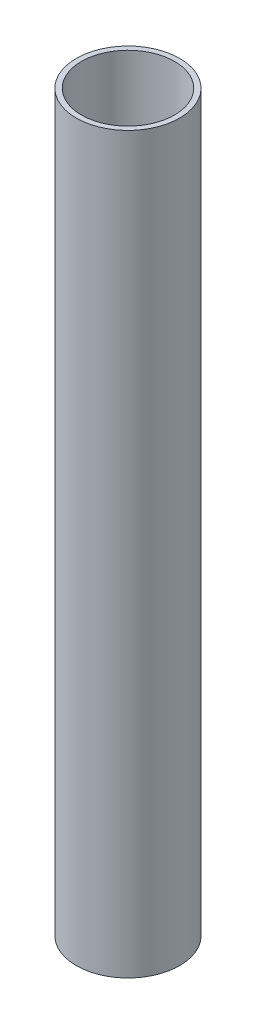
SolidWorks part; units mm, degrees
other "Boss-Extrude"
material "Toray T700"
ref_plane "Front" through (0, 0, 0) normal (0, 0, 1) x (1, 0, 0)
ref_plane "Top" through (0, 0, 0) normal (0, 1, 0) x (1, 0, 0)
ref_plane "Right" through (0, 0, 0) normal (1, 0, 0) x (0, 0, -1)
sketch "Sketch1" plane through (0, 0, 0) normal (0, 1, 0) x (1, 0, 0)
  line L5 (4.7969, 0) -> (-5.97, 0) construction
  circle A0 centre (0, 0) radius 10
  circle A1 centre (0, 0) radius 9
  dimension "D1" = 20
  dimension "D2" = 18
extrude "Boss-Extrude1" add sketch "Sketch1" along normal blind 142
ref_axis "Axis1" through (0, 0, 50) along (0, 0, -1)
ref_axis "Axis3" through (0, 142, 0) along (0, -1, 0)
